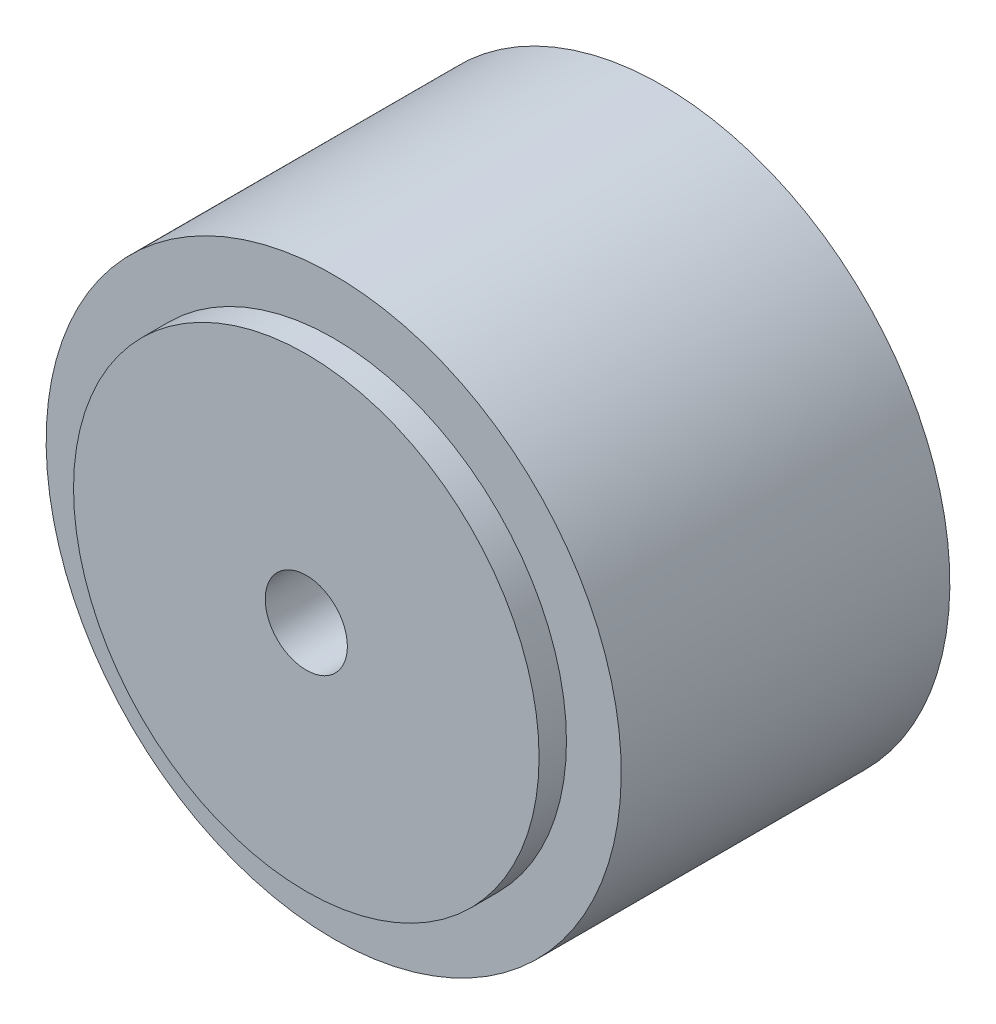
SolidWorks part; units mm, degrees
material "6061 Alloy"
ref_plane "Front" through (0, 0, 0) normal (0, 0, 1) x (1, 0, 0)
ref_plane "Top" through (0, 0, 0) normal (0, 1, 0) x (1, 0, 0)
ref_plane "Right" through (0, 0, 0) normal (1, 0, 0) x (0, 0, -1)
ref_axis "X" through (-80.9, 0, 0) along (1, 0, 0)
ref_axis "Y" through (0, -50, 0) along (0, 1, 0)
ref_axis "Z" through (0, 0, -80.9) along (0, 0, 1)
sketch "Sketch1" plane through (0, 0, 0) normal (1, 0, 0) x (0, 0, -1)
  line L0 (0, 0) -> (0, 8.5)
  line L1 (0, 8.5) -> (1, 8.5)
  line L2 (1, 8.5) -> (1, 10.5)
  line L3 (1, 10.5) -> (13, 10.5)
  line L4 (13, 10.5) -> (13, 8.5)
  line L5 (13, 8.5) -> (14, 8.5)
  line L6 (14, 8.5) -> (14, 5.5)
  line L7 (14, 5.5) -> (3, 5.5)
  line L8 (3, 5.5) -> (3, 0)
  line L9 (3, 0) -> (0, 0)
  line L10 (-21.2191, 0) -> (21.2191, 0) construction
  dimension "D1" = 21
  dimension "D2" = 12
  dimension "D3" = 14
  dimension "D4" = 2
  dimension "D5" = 3
revolve "Revolve1" add sketch "Sketch1" angle 360 about L10
hole_wizard "Ø3.0 (3) Diameter Hole1" positions "Sketch2" profile "Sketch3" hole size "Ø3.0" standard "ANSI Metric" end condition up to next
sketch "Sketch2" plane through (0, 0, 0) normal (0, 0, 1) x (1, 0, 0)
  point P0 (0, 0)
sketch "Sketch3" plane through (0, 0, 0) normal (1, 0, 0) x (0, -1, 0)
  line L0 (0, 0) -> (0, 3)
  line L1 (0, 3) -> (1.5, 3)
  line L2 (1.5, 3) -> (1.5, 0)
  line L5 (1.5, 0) -> (0, 0)
  line L11 (0, -6.35) -> (0, 107.95) construction
  dimension "Thru Hole Dia." = 3
  dimension "Thru Hole Depth" = 3
chamfer "Chamfer1" distance 1 angle 45 1 edges at (0, -5.5, -14)
